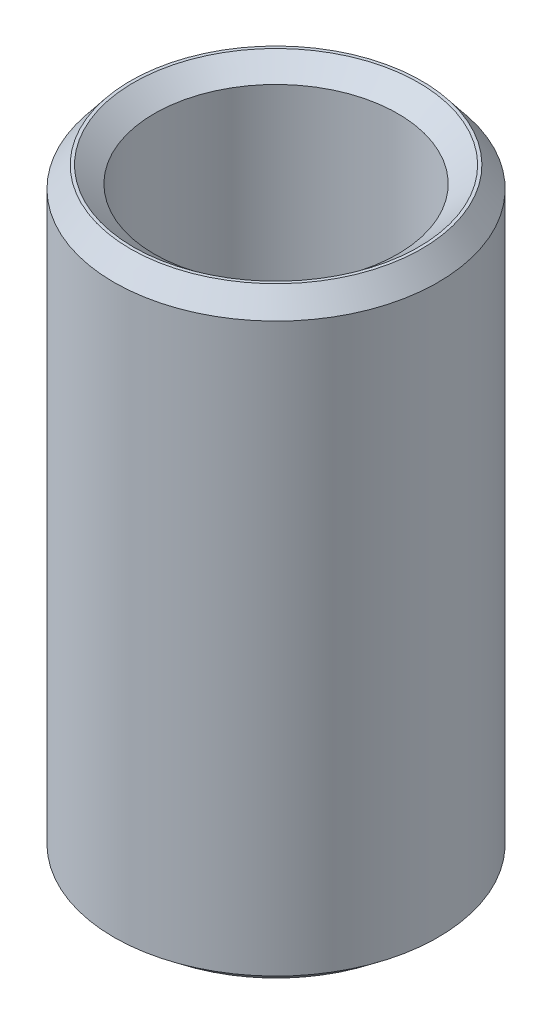
SolidWorks part; units mm, degrees
ref_plane "Front Plane" through (0, 0, 0) normal (0, 0, 1) x (1, 0, 0)
ref_plane "Top Plane" through (0, 0, 0) normal (0, 1, 0) x (1, 0, 0)
ref_plane "Right Plane" through (0, 0, 0) normal (1, 0, 0) x (0, 0, -1)
sketch "Sketch1" plane through (0, 0, 0) normal (0, 1, 0) x (1, 0, 0)
  circle A0 centre (0, 0) radius 25
  dimension "SLEEVE_OD" = 50
extrude "Boss-Extrude1" add sketch "Sketch1" along normal blind 93.2746
sketch "Sketch2" plane through (0, 0, 0) normal (0, 1, 0) x (1, 0, 0)
  circle A0 centre (0, 0) radius 18.7879
  dimension "BORE_D" = 37.5759
extrude "Cut-Extrude1" cut sketch "Sketch2" along normal through all
chamfer "Chamfer1" distance 3.2082 angle 38.323 4 edges at (0, 93.2746, 18.7879) (0, 0, 18.7879) (0, 0, 25) (0, 93.2746, 25) first distance on face at (0, 93.2746, 18.7879) first distance on face at (0, 0, 18.7879) first distance on face at (0, 93.2746, 25)
